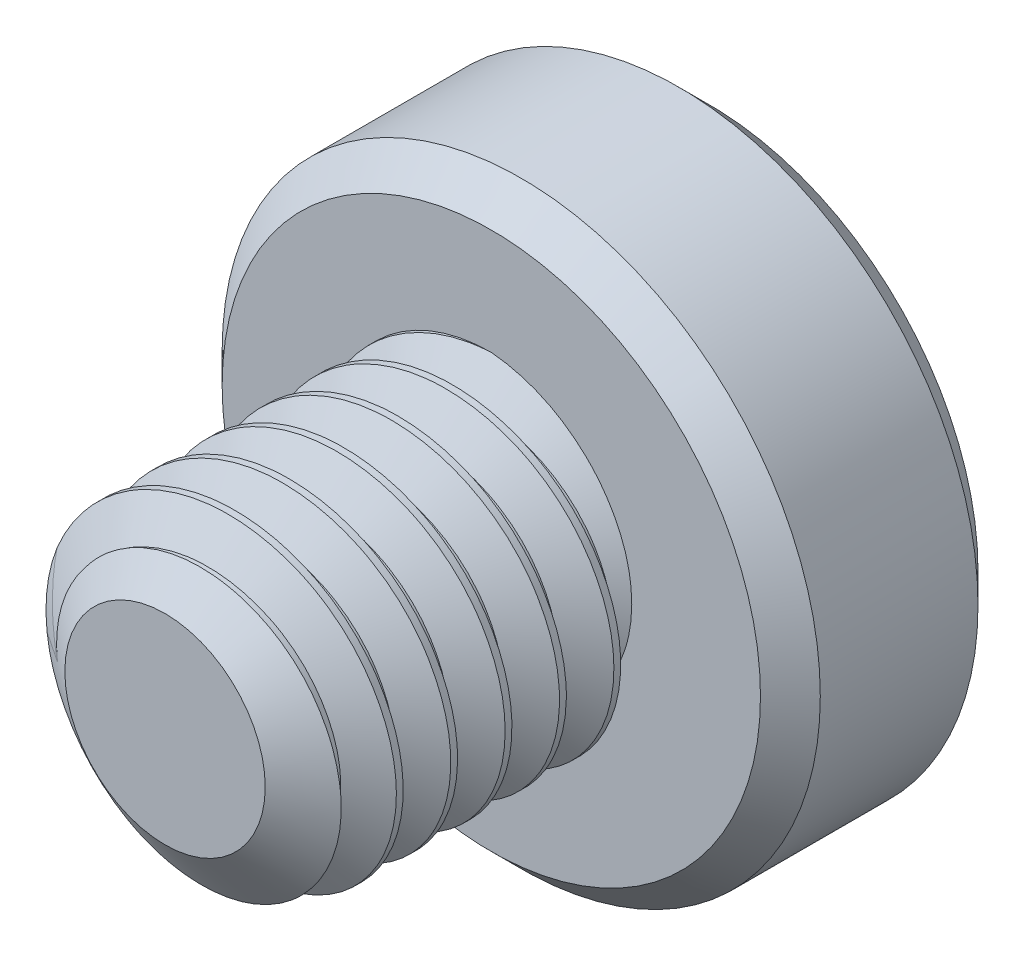
SolidWorks part; units mm, degrees
other "DetailItem1"
material "AISI Type 316L stainless steel"
ref_plane "Front Plane" through (0, 0, 0) normal (0, 0, 1) x (1, 0, 0)
ref_plane "Top Plane" through (0, 0, 0) normal (0, 1, 0) x (1, 0, 0)
ref_plane "Right Plane" through (0, 0, 0) normal (1, 0, 0) x (0, 0, -1)
sketch "Sketch1" plane through (0, 0, 0) normal (0, 0, 1) x (1, 0, 0)
  circle A0 centre (0, 0) radius 1.5
  dimension "OD" = 3
extrude "Extrude1" add sketch "Sketch1" against normal blind 3
sketch "Sketch2" plane through (0, 0, 0) normal (0, 0, 1) x (1, 0, 0)
  circle A0 centre (0, 0) radius 1.5 construction
  circle A1 centre (0, 0) radius 1.5
curve "Helix/Spiral1" pitch 0.5 height 3.5 radius 1.5 centre (0, 0, 0) axis (0, 0, -1) start towards (0, 1, 0) parameters "pitch"=0.5
sketch "Sketch3" plane through (0, 0, 0) normal (1, 0, 0) x (0, 0, -1)
  line L0 (-0.4375, 1.5) -> (-0.25, 1.1752)
  line L1 (-0.25, 1.1752) -> (-0.1875, 1.1752)
  line L2 (-0.1875, 1.1752) -> (0, 1.5)
  line L3 (-0.4375, 1.5) -> (0, 1.5)
  line L4 (-0.2188, 1.5) -> (-0.2188, 1.1752) construction
  line L5 (-0.3438, 1.3376) -> (-0.0938, 1.3376) construction
  line L6 (0, 1.5) -> (0, -1.5) construction
  dimension "D1" = 0.0625
  dimension "D2" = 0.25
  dimension "D3" = 60
sweep "Cut-Sweep1" cut profiles "Sketch3" path "Helix/Spiral1" align with end faces yes
sketch "Sketch4" plane through (0, 0, 0) normal (1, 0, 0) x (0, 0, -1)
  line L0 (0.4053, 1.5) -> (0, 0.9212)
  line L1 (0, 0.9212) -> (0, 1.5)
  line L2 (0.4053, 1.5) -> (0, 1.5)
  line L3 (-0.4375, 1.5) -> (0, 1.5) construction
  line L4 (0, 0) -> (7.0209, 0) construction
  dimension "D1" = 55
  dimension "D2" = 0.254
revolve "Cut-Revolve1" cut sketch "Sketch4" angle 360 about L4
sketch "Sketch6" plane through (0, 0, -3) normal (0, 0, -1) x (-1, 0, 0)
  circle A0 centre (0, 0) radius 2.75
  dimension "head dia" = 5.5
extrude "Extrude2" add sketch "Sketch6" along normal blind 2
sketch "Sketch7" plane through (0, 0, -5) normal (0, 0, -1) x (-1, 0, 0)
  line L1 (0, 1.1547) -> (-1, 0.5774)
  line L2 (-1, 0.5774) -> (-1, -0.5774)
  line L3 (-1, -0.5774) -> (0, -1.1547)
  line L4 (0, -1.1547) -> (1, -0.5774)
  line L5 (1, -0.5774) -> (1, 0.5774)
  line L6 (1, 0.5774) -> (0, 1.1547)
  circle A0 centre (0, 0) radius 1 construction
  dimension "hex dia" = 2
extrude "Cut-Extrude1" cut sketch "Sketch7" against normal blind 1.5
sketch "Sketch8" plane through (0, 0, -5) normal (0, 0, -1) x (-1, 0, 0)
  circle A0 centre (0, 0) radius 1.1547
extrude "Cut-Extrude2" cut sketch "Sketch8" against normal through all draft 45
chamfer "Chamfer1" distance 0.275 angle 45 2 edges at (-2.75, 0, -5) (-2.75, 0, -3)
sketch "Sketch10" plane through (0, 0, -3) normal (0, 0, 1) x (1, 0, 0)
  circle A1 centre (0, 0) radius 1.5
  circle A2 centre (0, 0) radius 1.5
  dimension "D1" = 0
ref_plane "Plane1" through (0, 0, -30) normal (0, 0, 1) x (1, 0, 0)
extrude "partial thread" [suppressed] add sketch "Sketch10" along normal up to surface (20 mm away) separate body up to plane "Plane1"
chamfer "Chamfer2" [suppressed] distance 0.06 angle 45
combine bodies "Combine1" [suppressed] operation type add bodies to combine 107 108
sketch "Sketch9" plane through (0, 0, 0) normal (1, 0, 0) x (0, 0, -1)
  line L0 (0, 1.5) -> (0, -1.5) construction
  line L1 (1.25, 1.5) -> (1.25, -1.5) construction
  dimension "D1" = 1.25
equation "\"D3@Helix/Spiral1\" = \"screw length@Extrude1\"+\"pitch@Helix/Spiral1\""
equation "\"D1@Sketch3\" = \"pitch@Helix/Spiral1\"*.125"
equation "\"D2@Sketch3\" = \"pitch@Helix/Spiral1\"*.5"
equation "\"D1@Cut-Extrude1\" = \"hex dia@Sketch7\"*.75"
equation "\"D1@Chamfer1\" = \"head dia@Sketch6\"*.05"
equation "\"D1@Sketch9\" = \"pitch@Helix/Spiral1\"*2.5"
equation "\"D1@Chamfer2\"=\"OD@Sketch1\"*.02"
